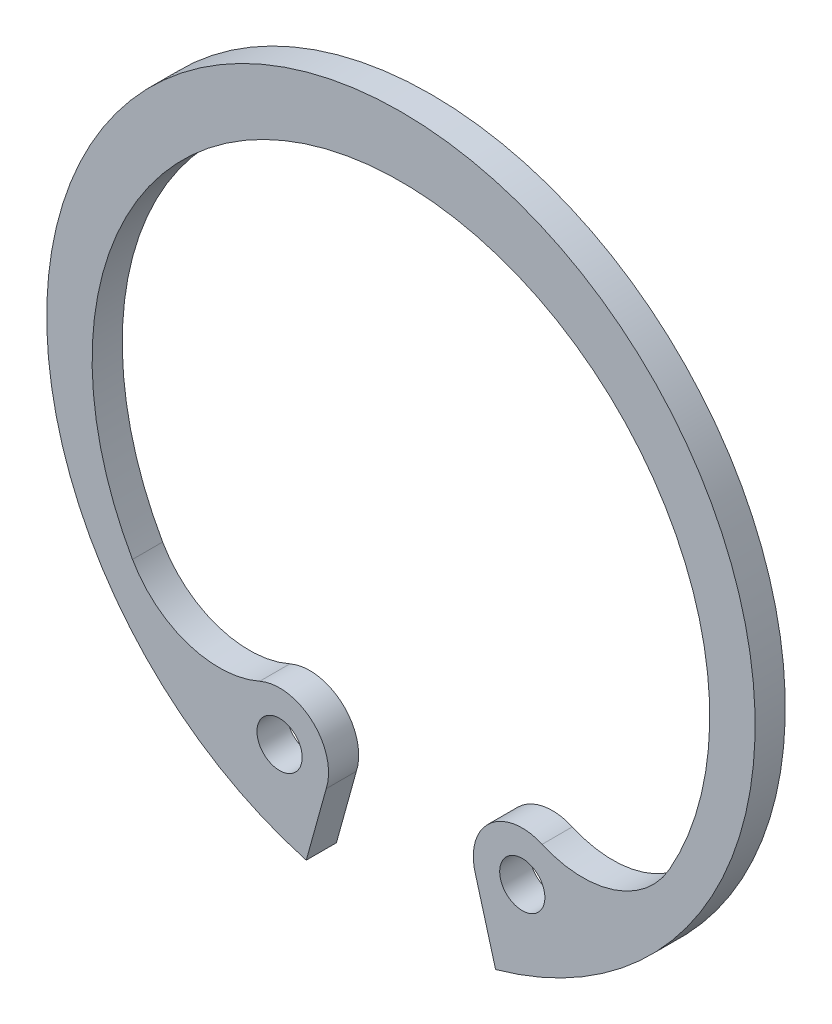
SolidWorks part; units mm, degrees
ref_plane "Front Plane" through (0, 0, 0) normal (0, 0, 1) x (1, 0, 0)
ref_plane "Top Plane" through (0, 0, 0) normal (0, 1, 0) x (1, 0, 0)
ref_plane "Right Plane" through (0, 0, 0) normal (1, 0, 0) x (0, 0, -1)
sketch "Sketch1" plane through (0, 0, 0) normal (0, 0, 1) x (1, 0, 0)
  line L0 (0, 0) -> (0, -11.75) construction
  line L1 (0, 0) -> (-3.1401, -11.3227) construction
  line L2 (0, 0) -> (-4.0253, -8.4392) construction
  line L3 (0, 0) -> (-8.9045, -5.5642) construction
  line L4 (-3.1401, -11.3227) -> (-2.4787, -8.9378)
  line L5 (3.1401, -11.3227) -> (2.4787, -8.9378)
  circle A4 centre (0, 0) radius 11.75 construction
  circle A5 centre (-4.0253, -8.4392) radius 0.75
  circle A6 centre (-4.0253, -8.4392) radius 1.625 construction
  arc A7 (-3.1401, -11.3227) -> (3.1401, -11.3227) centre (0, 0) cw
  arc A8 (-2.4787, -8.9378) -> (-4.6842, -6.9538) centre (-4.0253, -8.4392) ccw
  arc A9 (-4.6842, -6.9538) -> (-8.9045, -5.5642) centre (-6.0267, -3.9275) cw
  arc A10 (-8.9045, -5.5642) -> (8.9045, -5.5642) centre (0, -0.5) cw
  circle A11 centre (4.0253, -8.4392) radius 0.75
  arc A12 (2.4787, -8.9378) -> (4.6842, -6.9538) centre (4.0253, -8.4392) cw
  arc A13 (4.6842, -6.9538) -> (8.9045, -5.5642) centre (6.0267, -3.9275) ccw
  point P17 (0, 0)
  point P18 (0, 0)
  point P19 (0, 0)
  dimension "D1" = 23.5
  dimension "D2" = 15.5
  dimension "D7" = 1.5
  dimension "D8" = 10.5
  dimension "D6" = 3.25
  dimension "D9" = 0.5
  dimension "D3" = 25.5
  dimension "D4" = 58
  dimension "D5" = 9.35
base flange "Base-Flange1" sketch "Sketch1" thickness 1 reverse thickness direction no parameters "D1"=1
sketch "Bend-Lines1" [suppressed] plane through (0, 0, 0) normal (0, 1, 0) x (1, 0, 0)
sketch "Bounding-Box1" [suppressed] plane through (0, 0, 0) normal (0, 1, 0) x (1, 0, 0)
sheet metal parameters "Sheet-Metal1" thickness 1 parameters "D1"=1
flat pattern "Flat-Pattern1" [suppressed]
sketch "Bend-Lines2" plane through (0, 0, 0) normal (0, 1, 0) x (1, 0, 0)
sketch3d "Bounding-Box2" [suppressed]
  line L0 (11.75, -11.3227, 0) -> (-11.75, -11.3227, 0) construction
  line L1 (11.75, 11.7499, 0) -> (-11.75, 11.7499, 0) construction
  line L2 (11.75, -11.3227, 0) -> (11.75, 11.7499, 0) construction
  line L3 (-11.75, -11.3227, 0) -> (-11.75, 11.7499, 0) construction
